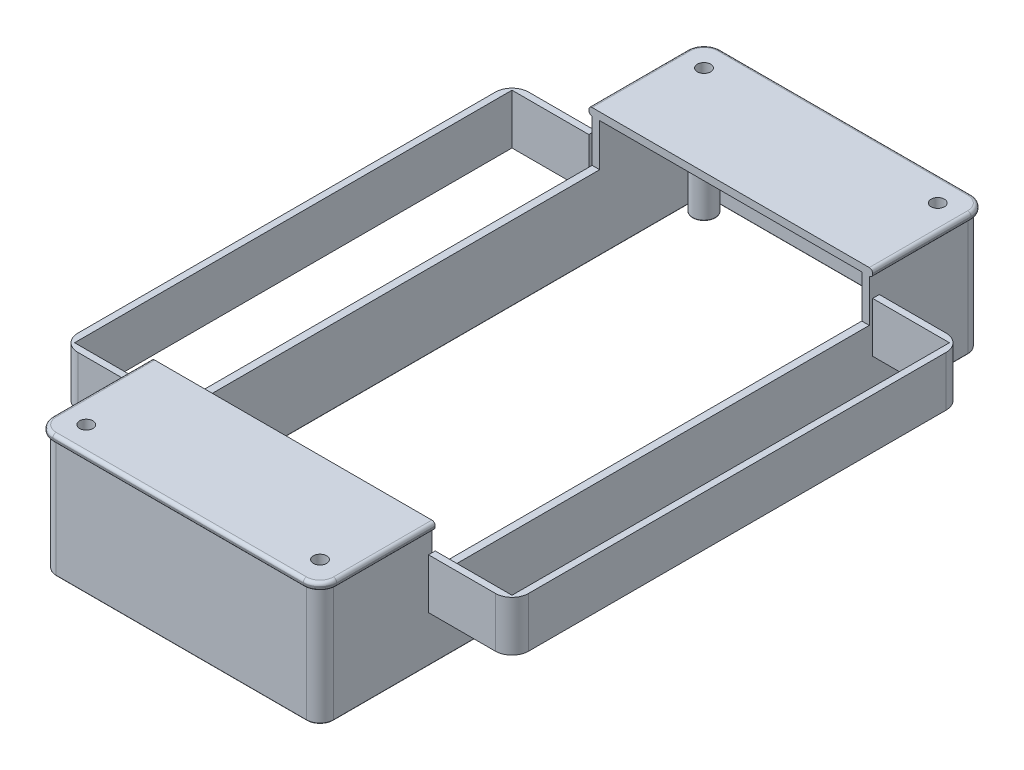
SolidWorks part; units mm, degrees
ref_plane "Front Plane" through (0, 0, 0) normal (0, 0, 1) x (1, 0, 0)
ref_plane "Top Plane" through (0, 0, 0) normal (0, 1, 0) x (1, 0, 0)
ref_plane "Right Plane" through (0, 0, 0) normal (1, 0, 0) x (0, 0, -1)
sketch "Sketch1" plane through (0, 0, 0) normal (0, 1, 0) x (1, 0, 0)
  line L1 (-42.5, 100) -> (42.5, 100)
  line L2 (-42.5, 100) -> (-42.5, -100)
  line L3 (-42.5, -100) -> (42.5, -100)
  line L4 (42.5, 100) -> (42.5, -100)
  line L5 (-42.5, 100) -> (42.5, -100) construction
  line L6 (-42.5, -100) -> (42.5, 100) construction
  point P0 (0, 0)
  dimension "D1" = 200
  dimension "D2" = 85
extrude "Boss-Extrude1" add sketch "Sketch1" along normal blind 2.25
other "Freeze***"
sketch "Sketch2" plane through (0, 2.25, 0) normal (0, 1, 0) x (1, 0, 0)
  line L0 (0, 100) -> (0, 0) construction
  line L1 (42.5, 100) -> (-42.5, 100) construction
  line L2 (0, 0) -> (-71.1325, 0) construction
  circle A0 centre (-35, 92.5) radius 2
  circle A1 centre (35, 92.5) radius 2
  circle A14 centre (35, -92.5) radius 2
  circle A15 centre (-35, -92.5) radius 2
  dimension "D1" = 4
  dimension "D2" = 7.5
  dimension "D3" = 70
extrude "Cut-Extrude1" cut sketch "Sketch2" against normal up to surface (2.25 mm away) up to face at (0, 0, 0)
fillet "Fillet1" radius 5 4 edges at (-42.5, 1.125, -100) (42.5, 1.125, -100) (42.5, 1.125, 100) (-42.5, 1.125, 100)
fillet "Fillet2" radius 1 16 edges at (0, 2.25, -100) (41.0355, 2.25, -98.5355) (42.5, 2.25, 0) (41.0355, 2.25, 98.5355) (0, 2.25, 100) (-41.0355, 2.25, 98.5355) (-42.5, 2.25, 0) (41.0355, 0, -98.5355) (42.5, 0, 0) (41.0355, 0, 98.5355) (0, 0, 100) (-41.0355, 0, 98.5355) (-42.5, 0, 0) (-41.0355, 0, -98.5355) (-41.0355, 2.25, -98.5355) (0, 0, -100)
sketch "Sketch3" plane through (0, 0, 0) normal (0, -1, 0) x (1, 0, 0)
  line L8 (37.5, 96.75) -> (-37.5, 96.75)
  line L9 (-39.25, 95) -> (-39.25, -95)
  line L10 (-37.5, -96.75) -> (37.5, -96.75)
  line L11 (39.25, -95) -> (39.25, 95)
  line L16 (-37.5, -99) -> (37.5, -99)
  line L17 (41.5, -95) -> (41.5, 95)
  line L18 (37.5, 99) -> (-37.5, 99)
  line L19 (-41.5, 95) -> (-41.5, -95)
  line L20 (-37.5, -99) -> (37.5, -99)
  line L21 (41.5, -95) -> (41.5, 95)
  line L22 (37.5, 99) -> (-37.5, 99)
  line L23 (-41.5, 95) -> (-41.5, -95)
  arc A8 (-37.5, 96.75) -> (-39.25, 95) centre (-37.5, 95) ccw
  arc A9 (-39.25, -95) -> (-37.5, -96.75) centre (-37.5, -95) ccw
  arc A10 (37.5, -96.75) -> (39.25, -95) centre (37.5, -95) ccw
  arc A11 (39.25, 95) -> (37.5, 96.75) centre (37.5, 95) ccw
  arc A16 (37.5, -99) -> (41.5, -95) centre (37.5, -95) ccw
  arc A17 (41.5, 95) -> (37.5, 99) centre (37.5, 95) ccw
  arc A18 (-37.5, 99) -> (-41.5, 95) centre (-37.5, 95) ccw
  arc A19 (-41.5, -95) -> (-37.5, -99) centre (-37.5, -95) ccw
  arc A20 (37.5, -99) -> (41.5, -95) centre (37.5, -95) ccw
  arc A21 (41.5, 95) -> (37.5, 99) centre (37.5, 95) ccw
  arc A22 (-37.5, 99) -> (-41.5, 95) centre (-37.5, 95) ccw
  arc A23 (-41.5, -95) -> (-37.5, -99) centre (-37.5, -95) ccw
  dimension "D1" = 0
  dimension "D2" = 2.25
extrude "Boss-Extrude2" add sketch "Sketch3" along normal blind 35
sketch "Sketch4" plane through (0, 0, 0) normal (0, -1, 0) x (1, 0, 0)
  circle A0 centre (35, 92.5) radius 2 construction
  circle A1 centre (35, -92.5) radius 2 construction
  circle A2 centre (-35, -92.5) radius 2 construction
  circle A3 centre (-35, 92.5) radius 2 construction
  circle A4 centre (35, 92.5) radius 2
  circle A5 centre (35, -92.5) radius 2
  circle A6 centre (-35, -92.5) radius 2
  circle A7 centre (-35, 92.5) radius 2
  circle A8 centre (-35, 92.5) radius 3.4
  circle A9 centre (35, 92.5) radius 3.4
  circle A10 centre (-35, -92.5) radius 3.4
  circle A11 centre (35, -92.5) radius 3.4
  dimension "D1" = 1.4
extrude "Boss-Extrude3" add sketch "Sketch4" along normal up to surface (35 mm away) up to face at (0, -35, 0)
fillet "Fillet3" radius 0.2 23 edges at (35, -35, 90.5) (-35, -35, 89.1) (-35, -35, 90.5) (-35, -35, -95.9) (-35, -35, -94.5) (-38.7374, -35, 96.2374) (-39.25, -35, 0) (-38.7374, -35, -96.2374) (0, -35, -96.75) (38.7374, -35, -96.2374) (39.25, -35, 0) (38.7374, -35, 96.2374) (0, -35, 96.75) (-41.5, -35, 0) (-40.3284, -35, 97.8284) (0, -35, 99) (40.3284, -35, 97.8284) (41.5, -35, 0) (40.3284, -35, -97.8284) (0, -35, -99) (-40.3284, -35, -97.8284) (35, -35, -95.9) (35, -35, -94.5)
sketch "Sketch5" plane through (0, 2.25, 0) normal (0, 1, 0) x (1, 0, 0)
  line L1 (-65.5, 65.5) -> (65.5, 65.5)
  line L2 (-65.5, 65.5) -> (-65.5, -65.5)
  line L3 (-65.5, -65.5) -> (65.5, -65.5)
  line L4 (65.5, 65.5) -> (65.5, -65.5)
  line L5 (-65.5, 65.5) -> (65.5, -65.5) construction
  line L6 (-65.5, -65.5) -> (65.5, 65.5) construction
  point P0 (0, 0)
  dimension "D1" = 131
  dimension "D2" = 131
extrude "Cut-Extrude2" cut sketch "Sketch5" against normal blind 15
sketch "Sketch6" plane through (0, -12.75, 0) normal (0, 1, 0) x (1, 0, 0)
  line L0 (-65.5, -65.5) -> (65.5, -65.5) construction
  line L1 (-65.5, -65.5) -> (-42.5, -65.5)
  line L2 (65.5, 65.5) -> (65.5, -65.5) construction
  line L3 (65.5, 65.5) -> (65.5, -65.5)
  line L4 (-65.5, 65.5) -> (-65.5, -65.5) construction
  line L5 (-65.5, 65.5) -> (-65.5, -65.5)
  line L6 (-65.5, 65.5) -> (65.5, 65.5) construction
  line L7 (-65.5, 65.5) -> (-42.5, 65.5)
  line L8 (-67.5, 67.5) -> (-67.5, -67.5)
  line L9 (-67.5, -67.5) -> (-42.5, -67.5)
  line L10 (67.5, 67.5) -> (67.5, -67.5)
  line L11 (-67.5, 67.5) -> (-42.5, 67.5)
  line L12 (-42.5, 67.5) -> (-42.5, 65.5)
  line L13 (-42.5, 65.5) -> (-42.5, 95) construction
  line L17 (-42.5, -65.5) -> (-42.5, -67.5)
  line L18 (42.5, -67.5) -> (42.5, -65.5)
  line L19 (42.5, -65.5) -> (42.5, -95) construction
  line L23 (42.5, 65.5) -> (42.5, 67.5)
  line L24 (42.5, 95) -> (42.5, 65.5) construction
  line L25 (42.5, 67.5) -> (67.5, 67.5)
  line L26 (-67.5, 67.5) -> (67.5, 67.5) construction
  line L27 (42.5, 65.5) -> (65.5, 65.5)
  line L28 (-65.5, 65.5) -> (65.5, 65.5) construction
  line L29 (42.5, -67.5) -> (67.5, -67.5)
  line L30 (-67.5, -67.5) -> (67.5, -67.5) construction
  line L31 (42.5, -65.5) -> (65.5, -65.5)
  line L32 (-65.5, -65.5) -> (65.5, -65.5) construction
  dimension "D1" = 2
extrude "Boss-Extrude4" add sketch "Sketch6" along normal mid plane 15 separate body
fillet "Fillet4" radius 5 2 edges at (-67.5, -12.75, -67.5) (-67.5, -12.75, 67.5)
fillet "Fillet5" radius 5 2 edges at (67.5, -12.75, 67.5) (67.5, -12.75, -67.5)
